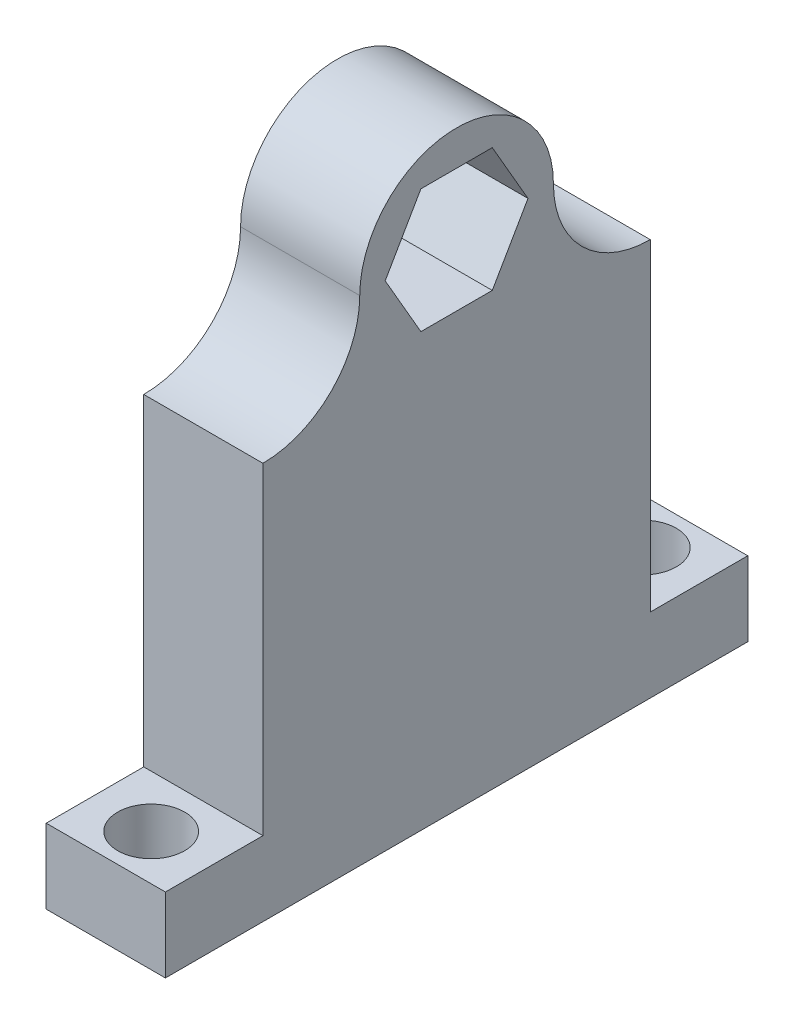
SolidWorks part; units mm, degrees
ref_plane "Спереди" through (0, 0, 0) normal (0, 0, 1) x (1, 0, 0)
ref_plane "Сверху" through (0, 0, 0) normal (0, 1, 0) x (1, 0, 0)
ref_plane "Справа" through (0, 0, 0) normal (1, 0, 0) x (0, 0, -1)
sketch "Эскиз1" plane through (0, 0, 0) normal (1, 0, 0) x (0, 0, -1)
  line L6 (-6.5, 0) -> (6.5, 0) construction
  line L12 (-13, -6.5) -> (-13, -11.5)
  line L13 (13, -6.5) -> (13, -11.5)
  line L15 (-13, -11.5) -> (13, -11.5)
  arc A0 (6.5, 0) -> (-6.5, 0) centre (0, 0) ccw
  arc A1 (-13, -6.5) -> (-6.5, 0) centre (-13, 0) ccw
  arc A2 (6.5, 0) -> (13, -6.5) centre (13, 0) ccw
  point P4 (0, 0)
  point P7 (0, -39.795)
  point P9 (0, 6.5)
  dimension "D1" = 13
  dimension "D4" = 13
  dimension "D5" = 13
  dimension "D2" = 5
extrude "Бобышка-Вытянуть1" add sketch "Эскиз1" along normal blind 8
sketch "Эскиз2" plane through (8, 0, 0) normal (1, 0, 0) x (0, 0, -1)
  line L1 (4.792, 0) -> (2.396, 4.15)
  line L2 (2.396, 4.15) -> (-2.396, 4.15)
  line L3 (-2.396, 4.15) -> (-4.792, 0)
  line L4 (-4.792, 0) -> (-2.396, -4.15)
  line L5 (-2.396, -4.15) -> (2.396, -4.15)
  line L6 (2.396, -4.15) -> (4.792, 0)
  circle A0 centre (0, 0) radius 4.15 construction
  dimension "D1" = 8.3
extrude "Вырез-Вытянуть1" cut sketch "Эскиз2" against normal through all
sketch "Эскиз4" plane through (0, -11.5, 0) normal (0, -1, 0) x (1, 0, 0)
  line L8 (0, 13) -> (0, -13)
  line L9 (0, -13) -> (8, -13)
  line L10 (8, -13) -> (8, 13)
  line L11 (8, 13) -> (0, 13)
  line L12 (0, 13) -> (0, -13)
  line L13 (0, -13) -> (8, -13)
  line L14 (8, -13) -> (8, 13)
  line L15 (8, 13) -> (0, 13)
  dimension "D1" = 0
extrude "Бобышка-Вытянуть2" add sketch "Эскиз4" along normal up to surface (21.65 mm away)
sketch "Эскиз5" plane through (0, -33.15, 0) normal (0, -1, 0) x (1, 0, 0)
  line L0 (0, 13) -> (0, -13) construction
  line L1 (0, 19.5455) -> (8, 19.5455)
  line L2 (0, 19.5455) -> (0, -19.5455)
  line L3 (0, -19.5455) -> (8, -19.5455)
  line L4 (8, 19.5455) -> (8, -19.5455)
  line L5 (8, -13) -> (8, 13) construction
  line L6 (534, -19.5455) -> (-10, -19.5455) construction
  line L7 (534, 19.5455) -> (-10, 19.5455) construction
  line L8 (4, -16.5) -> (4, 16.5) construction
  line L9 (8, -19.5455) -> (0, 19.5455) construction
  line L10 (0, -19.5455) -> (8, 19.5455) construction
  circle A0 centre (4, -16.5) radius 2.25
  circle A1 centre (4, 16.5) radius 2.25
  point P16 (4, 0)
  point P17 (8, 0)
  point P18 (4, 0)
  dimension "D1" = 4.5
  dimension "D2" = 4.5
  dimension "D3" = 33
extrude "Бобышка-Вытянуть3" add sketch "Эскиз5" against normal blind 5
